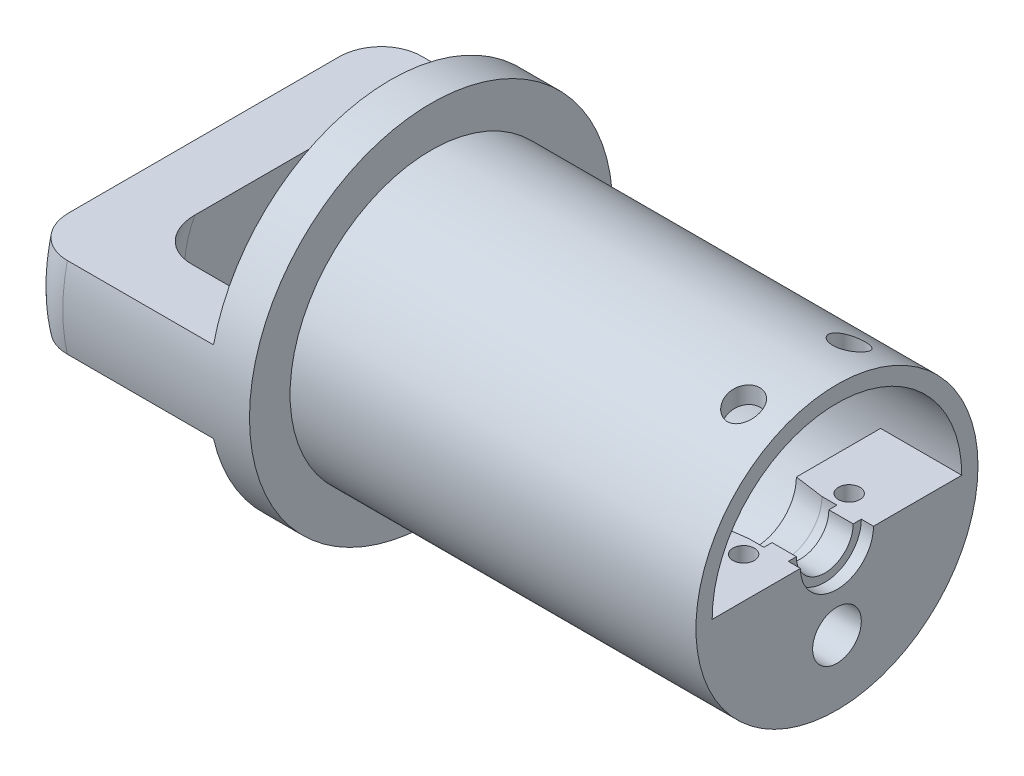
SolidWorks part; units mm, degrees
ref_plane "Plan de face" through (0, 0, 0) normal (0, 0, 1) x (1, 0, 0)
ref_plane "Plan de dessus" through (0, 0, 0) normal (0, 1, 0) x (1, 0, 0)
ref_plane "Plan de droite" through (0, 0, 0) normal (1, 0, 0) x (0, 0, -1)
sketch "Esquisse1" plane through (0, 0, 0) normal (0, 0, 1) x (1, 0, 0)
  line L0 (0, 0) -> (-396.8389, 0) construction
  line L1 (0, 0) -> (0, 34.75)
  line L2 (0, 34.75) -> (-100, 34.75)
  line L3 (-100, 34.75) -> (-100, 44.75)
  line L4 (-100, 44.75) -> (-110, 44.75)
  line L5 (-110, 44.75) -> (-110, 0)
  line L6 (0, 0) -> (-110, 0)
  dimension "D1" = 34.75
  dimension "D2" = 100
  dimension "D3" = 10
  dimension "D4" = 44.75
revolve "Révolution1" add sketch "Esquisse1" angle 360 about L0
sketch "Esquisse2" plane through (0, 0, 0) normal (1, 0, 0) x (0, 0, -1)
  circle A0 centre (0, 0) radius 30.75
  dimension "D1" = 61.5
extrude "Enlèv. mat.-Extru.1" cut sketch "Esquisse2" against normal through all from offset 20 offset against normal yes
sketch "Esquisse3" plane through (-20, 0, 0) normal (-1, 0, 0) x (0, 0, 1)
  line L0 (-30.75, 0) -> (30.75, 0)
  circle A0 centre (0, 0) radius 30.75 construction
  circle A1 centre (0, 0) radius 30.75 construction
  arc A2 (30.75, 0) -> (-30.75, 0) centre (0, 0) ccw
extrude "Enlèv. mat.-Extru.2" cut sketch "Esquisse3" against normal blind 20
sketch "Esquisse4" plane through (0, 0, 0) normal (0, 1, 0) x (1, 0, 0)
  line L0 (0, 0) -> (-20, 0) construction
  line L1 (-20, 30.75) -> (-20, -30.75) construction
  line L2 (0, 0) -> (0, 9)
  line L3 (0, 30.75) -> (0, -30.75) construction
  line L4 (0, 9) -> (-3, 9)
  line L5 (-3, 9) -> (-3, 7)
  line L6 (-3, 7) -> (-9, 7)
  line L7 (-9, 7) -> (-9, 9)
  line L8 (-9, 9) -> (-12.7, 9)
  line L9 (-12.7, 9) -> (-20, 10)
  line L10 (-20, 10) -> (-20, 0)
  line L11 (-20, 0) -> (0, 0)
  dimension "D1" = 9
  dimension "D2" = 7
  dimension "D3" = 9
  dimension "D4" = 10
  dimension "D5" = 3
  dimension "D6" = 6
  dimension "D7" = 3.7
revolve "Enlèvement de matière-Révolution1" cut sketch "Esquisse4" angle 360 about L11
sketch "Esquisse5" plane through (0, 0, 0) normal (0, 1, 0) x (1, 0, 0)
  line L0 (0, -9) -> (0, -30.75) construction
  line L1 (0, 30.75) -> (0, 9) construction
  circle A0 centre (-10, -13) radius 2.65
  circle A1 centre (-10, 13) radius 2.65
  dimension "D1" = 10
  dimension "D2" = 13
  dimension "D3" = 10
  dimension "D4" = 13
  dimension "D5" = 5.3
  dimension "D6" = 5.3
extrude "Enlèv. mat.-Extru.3" cut sketch "Esquisse5" against normal blind 6
sketch "Esquisse6" plane through (-20, 0, 0) normal (-1, 0, 0) x (0, 0, 1)
  line L0 (15.65, -6) -> (10.35, -6) construction
  line L1 (17, -6) -> (9, -6)
  line L2 (17, -6) -> (17, -11)
  line L3 (17, -11) -> (9, -11)
  line L4 (9, -6) -> (9, -11)
  line L5 (17, -6) -> (9, -11) construction
  line L6 (17, -11) -> (9, -6) construction
  line L8 (15.65, -2.2853) -> (10.35, -2.2853) construction
  line L9 (15.65, -6) -> (15.65, 0) construction
  line L10 (10.35, 0) -> (10.35, -6) construction
  line L11 (13, -2.2853) -> (13, -4.2509) construction
  line L12 (0, 0) -> (0, -17.4203) construction
  line L13 (-9, -6) -> (-9, -11)
  line L14 (-17, -6) -> (-17, -11)
  line L15 (-17, -11) -> (-9, -11)
  line L16 (-17, -6) -> (-9, -6)
  point P0 (13, -8.5)
  dimension "D1" = 8
  dimension "D2" = 5
  dimension "D3" = 4
extrude "Enlèv. mat.-Extru.4" cut sketch "Esquisse6" against normal blind 15
sketch "Esquisse7" plane through (-110, 0, 0) normal (-1, 0, 0) x (0, 0, 1)
  line L0 (-44.75, 0) -> (44.75, 0) construction
  line L1 (-29.0786, 10) -> (-43.6184, 10)
  line L2 (-29.0786, -10) -> (-43.6184, -10)
  line L3 (29.0786, 10) -> (43.6184, 10)
  line L4 (29.0786, -10) -> (43.6184, -10)
  circle A0 centre (0, 0) radius 44.75 construction
  circle A1 centre (0, 0) radius 30.75 construction
  arc A2 (-43.6184, 10) -> (-43.6184, -10) centre (0, 0) ccw
  arc A3 (-29.0786, 10) -> (-29.0786, -10) centre (0, 0) ccw
  arc A4 (29.0786, -10) -> (29.0786, 10) centre (0, 0) ccw
  arc A5 (43.6184, -10) -> (43.6184, 10) centre (0, 0) ccw
  dimension "D1" = 10
  dimension "D2" = 10
  dimension "D3" = 10
  dimension "D4" = 10
extrude "Boss.-Extru.1" add sketch "Esquisse7" along normal blind 30
sketch "Esquisse8" plane through (-140, 0, 0) normal (-1, 0, 0) x (0, 0, 1)
  line L1 (-43.6184, 10) -> (43.6184, 10)
  line L2 (-43.6184, 10) -> (-43.6184, -10)
  line L3 (-43.6184, -10) -> (43.6184, -10)
  line L4 (43.6184, 10) -> (43.6184, -10)
extrude "Boss.-Extru.2" add sketch "Esquisse8" along normal blind 16
sketch "Esquisse9" plane through (-140, 0, 0) normal (-1, 0, 0) x (0, 0, 1)
  line L1 (-43.6184, -10) -> (-43.6184, 10)
  line L2 (-43.6184, -10) -> (-43.6184, 10)
  arc A1 (-43.6184, 10) -> (-43.6184, -10) centre (0, 0) ccw
  arc A2 (-43.6184, 10) -> (-43.6184, -10) centre (0, 0) ccw
  dimension "D1" = 0
extrude "Boss.-Extru.3" add sketch "Esquisse9" along normal blind 16
sketch "Esquisse10" plane through (-140, 0, 0) normal (-1, 0, 0) x (0, 0, 1)
  line L1 (43.6184, 10) -> (43.6184, -10)
  line L2 (43.6184, 10) -> (43.6184, -10)
  arc A1 (43.6184, -10) -> (43.6184, 10) centre (0, 0) ccw
  arc A2 (43.6184, -10) -> (43.6184, 10) centre (0, 0) ccw
  dimension "D1" = 0
extrude "Boss.-Extru.4" add sketch "Esquisse10" along normal blind 16
fillet "Congé1" radius 10 4 edges at (-140, 0, 30.75) (-140, 0, -30.75) (-156, 0, -44.75) (-156, 0, 44.75)
ref_plane "Plan1" through (0, 34.75, 0) normal (0, 1, 0) x (1, 0, 0)
sketch "Esquisse11" plane through (0, 34.75, 0) normal (0, 1, 0) x (1, 0, 0)
  circle A0 centre (-10, 13) radius 4
  circle A1 centre (-10, -13) radius 4
  dimension "D1" = 8
  dimension "D2" = 8
extrude "Enlèv. mat.-Extru.5" cut sketch "Esquisse11" against normal blind 16
sketch "Esquisse12" plane through (0, 0, 0) normal (1, 0, 0) x (0, 0, -1)
  line L0 (0, 0) -> (0, -34.75) construction
  circle A0 centre (0, 0) radius 34.75 construction
  circle A1 centre (0, -18.75) radius 6
  dimension "D1" = 18.75
  dimension "D2" = 12
extrude "Enlèv. mat.-Extru.6" cut sketch "Esquisse12" against normal blind 16
